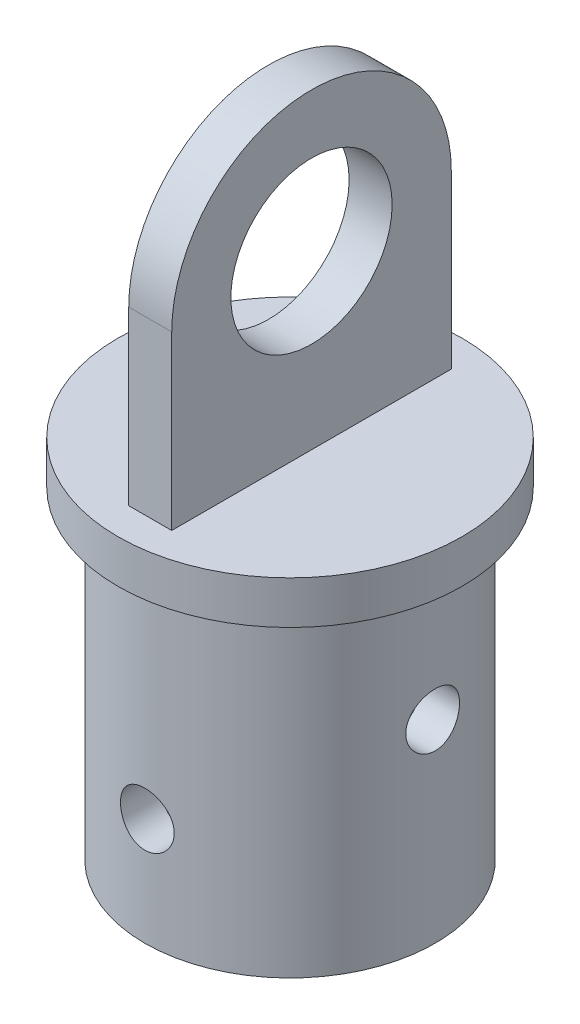
SolidWorks part; units mm, degrees
ref_plane "Front Plane" through (0, 0, 0) normal (0, 0, 1) x (1, 0, 0)
ref_plane "Top Plane" through (0, 0, 0) normal (0, 1, 0) x (1, 0, 0)
ref_plane "Right Plane" through (0, 0, 0) normal (1, 0, 0) x (0, 0, -1)
sketch "Sketch1" plane through (0, 0, 0) normal (0, 1, 0) x (1, 0, 0)
  circle A0 centre (0, 0) radius 16
  circle A1 centre (0, 0) radius 13.5
  circle A2 centre (0, 0) radius 10
  dimension "D1" = 20
  dimension "D2" = 27
  dimension "D3" = 32
extrude "Boss-Extrude1" add sketch "Sketch1" along normal blind 30 contours A1 A2 region at (-13.1182, 0, 0)
extrude "Boss-Extrude2" add sketch "Sketch1<3>" along normal blind 4 from offset 30 contours A0 A1 | A1 A2 | A2 region at (-15.5475, 0, 0) region at (-13.1182, 0, 0) region at (0, 0, 0)
sketch "Sketch1<3>" plane through (0, 0, 0) normal (0, 1, 0) x (1, 0, 0) same geometry as "Sketch1"
sketch "Sketch2" plane through (0, 0, 0) normal (1, 0, 0) x (0, 0, -1)
  line L0 (13, 50) -> (13, 34)
  line L1 (16, 34) -> (-16, 34) construction
  line L2 (-13, 50) -> (-13, 34)
  line L3 (-16, 30) -> (16, 30) construction
  line L4 (13, 34) -> (-13, 34)
  circle A0 centre (0, 18) radius 2.5
  circle A1 centre (0, 50) radius 7.5
  arc A2 (13, 50) -> (-13, 50) centre (0, 50) ccw
  dimension "D1" = 5
  dimension "D2" = 12
  dimension "D3" = 26
  dimension "D4" = 15
  dimension "D5" = 16
extrude "Boss-Extrude3" add sketch "Sketch2" along normal mid plane 4 contours L0 A2 L2 L4 A1 region at (0, 42, -12.6105)
extrude "Cut-Extrude1" cut sketch "Sketch2<3>" along normal up to next contours A0
sketch "Sketch2<3>" plane through (0, 0, 0) normal (1, 0, 0) x (0, 0, -1) same geometry as "Sketch2"
sketch "Sketch3" plane through (0, 0, 0) normal (0, 0, 1) x (1, 0, 0)
  line L0 (-10, 30) -> (10, 30) construction
  circle A0 centre (0, 10) radius 2.5
  point P2 (0, 0)
  point P5 (0, 0)
  dimension "D1" = 5
  dimension "D2" = 20
extrude "Cut-Extrude2" cut sketch "Sketch3" against normal through all both and the other way through all
